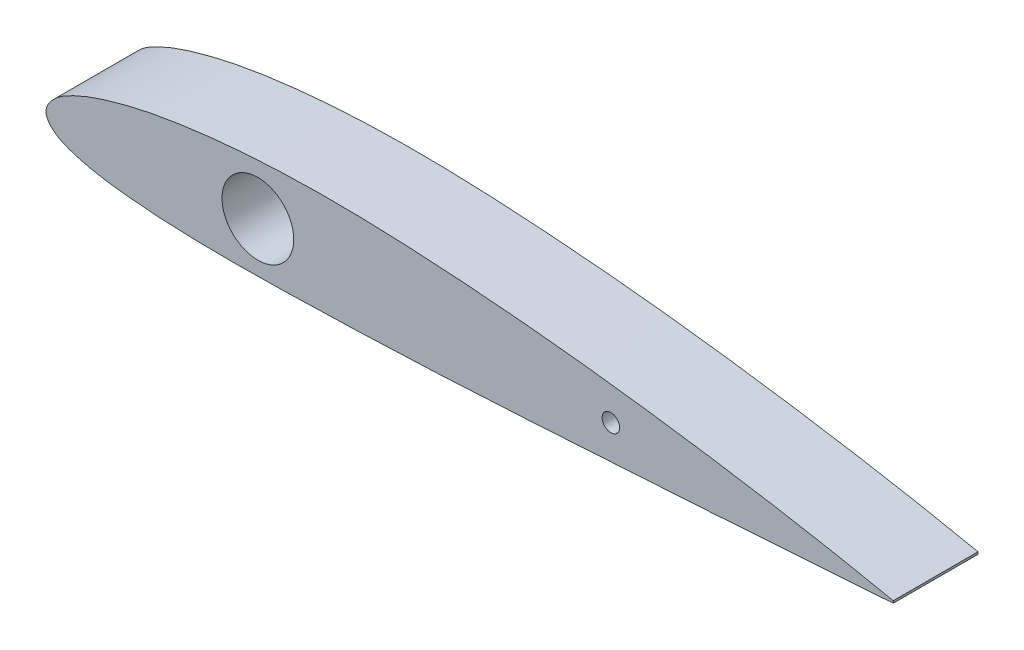
SolidWorks part; units mm, degrees
ref_plane "Front Plane" through (0, 0, 0) normal (0, 0, 1) x (1, 0, 0)
ref_plane "Top Plane" through (0, 0, 0) normal (0, 1, 0) x (1, 0, 0)
ref_plane "Right Plane" through (0, 0, 0) normal (1, 0, 0) x (0, 0, -1)
curve "Curve1"
  spline degree 3 poles (1, 0.0013, 0) (0.9833, 0.0047, 0) (0.9501, 0.0115, 0) (0.8835, 0.024, 0) (0.8002, 0.0379, 0) (0.7002, 0.0522, 0) (0.6002, 0.0641, 0) (0.5001, 0.0729, 0) (0.4001, 0.0788, 0) (0.3166, 0.0798, 0) (0.2499, 0.077, 0) (0.1999, 0.073, 0) (0.1498, 0.0666, 0) (0.108, 0.0587, 0) (0.0748, 0.0498, 0) (0.0496, 0.0416, 0) (0.0282, 0.0322, 0) (0.0098, 0.0207, 0) (-0.0063, 0.0009, 0) (0.0104, -0.0165, 0) (0.0285, -0.0245, 0) (0.0497, -0.0305, 0) (0.0749, -0.0348, 0) (0.1083, -0.0385, 0) (0.1499, -0.0414, 0) (0.2, -0.0425, 0) (0.25, -0.0424, 0) (0.3167, -0.0409, 0) (0.4, -0.0382, 0) (0.5, -0.0336, 0) (0.6, -0.0276, 0) (0.7, -0.0214, 0) (0.8, -0.0151, 0) (0.8833, -0.0093, 0) (0.95, -0.0048, 0) (0.9833, -0.0025, 0) (1, -0.0013, 0) knots 0 0 0 0 0.025012 0.049959 0.099673 0.149206 0.198581 0.247805 0.296917 0.345953 0.370492 0.395091 0.419815 0.444799 0.45749 0.470406 0.483879 0.491264 0.503459 0.513609 0.520451 0.533235 0.545691 0.558032 0.582609 0.607135 0.631652 0.656174 0.705234 0.75432 0.803437 0.852566 0.901701 0.950849 0.975423 1 1 1 1
sketch "Sketch1" plane through (0, 0, 0) normal (0, 0, 1) x (1, 0, 0)
  line L0 (-30.2439, 0) -> (269.7561, 0) construction
  line L1 (269.7561, 0.39) -> (269.7561, -0.39)
  circle A0 centre (44.7561, 5) radius 12.7
  circle A1 centre (169.7561, 5) radius 3.1
  spline S1 degree 3 poles (269.7561, 0.39) (264.7588, 1.414) (254.7775, 3.4593) (234.7977, 7.2056) (209.8095, 11.3564) (179.8038, 15.6525) (149.8031, 19.2352) (119.7893, 21.8586) (89.7824, 23.6351) (64.7467, 23.9358) (44.7379, 23.1075) (29.719, 21.8937) (14.6812, 19.9716) (2.166, 17.6048) (-7.8114, 14.927) (-15.3757, 12.4925) (-21.7845, 9.6559) (-27.3126, 6.2169) (-32.1334, 0.2696) (-27.1259, -4.9579) (-21.7011, -7.3422) (-15.3205, -9.1532) (-7.7812, -10.4518) (2.2361, -11.56) (14.7402, -12.4129) (29.7543, -12.7549) (44.7577, -12.7072) (64.7596, -12.2657) (89.7642, -11.4712) (119.7661, -10.0886) (149.7593, -8.2916) (179.7575, -6.4237) (209.7609, -4.5329) (234.7555, -2.7916) (254.7573, -1.4485) (264.7563, -0.7428) (269.7561, -0.39) knots 0 0 0 0 0.025012 0.049959 0.099673 0.149206 0.198581 0.247805 0.296917 0.345953 0.370492 0.395091 0.419815 0.444799 0.45749 0.470406 0.483879 0.491264 0.503459 0.513609 0.520451 0.533235 0.545691 0.558032 0.582609 0.607135 0.631652 0.656174 0.705234 0.75432 0.803437 0.852566 0.901701 0.950849 0.975423 1 1 1 1
  point P3 (44.7561, 5)
  point P7 (184.2743, 2.2022)
  point P8 (182.5461, 2.0361)
  point P9 (169.5802, 3.8935)
  point P10 (0, 0)
  point P11 (194.7561, 0)
  point P12 (0, 0)
  point P13 (169.7561, 5)
  point P14 (0, 0)
  point P17 (169.7561, 5)
  point P18 (0, 0)
  dimension "D3" = 75
  dimension "D4" = 25.4
  dimension "D1" = 6.2
  dimension "D2" = 5
  dimension "D5" = 75
  dimension "D6" = 25
extrude "Boss-Extrude1" add sketch "Sketch1" along normal blind 30
